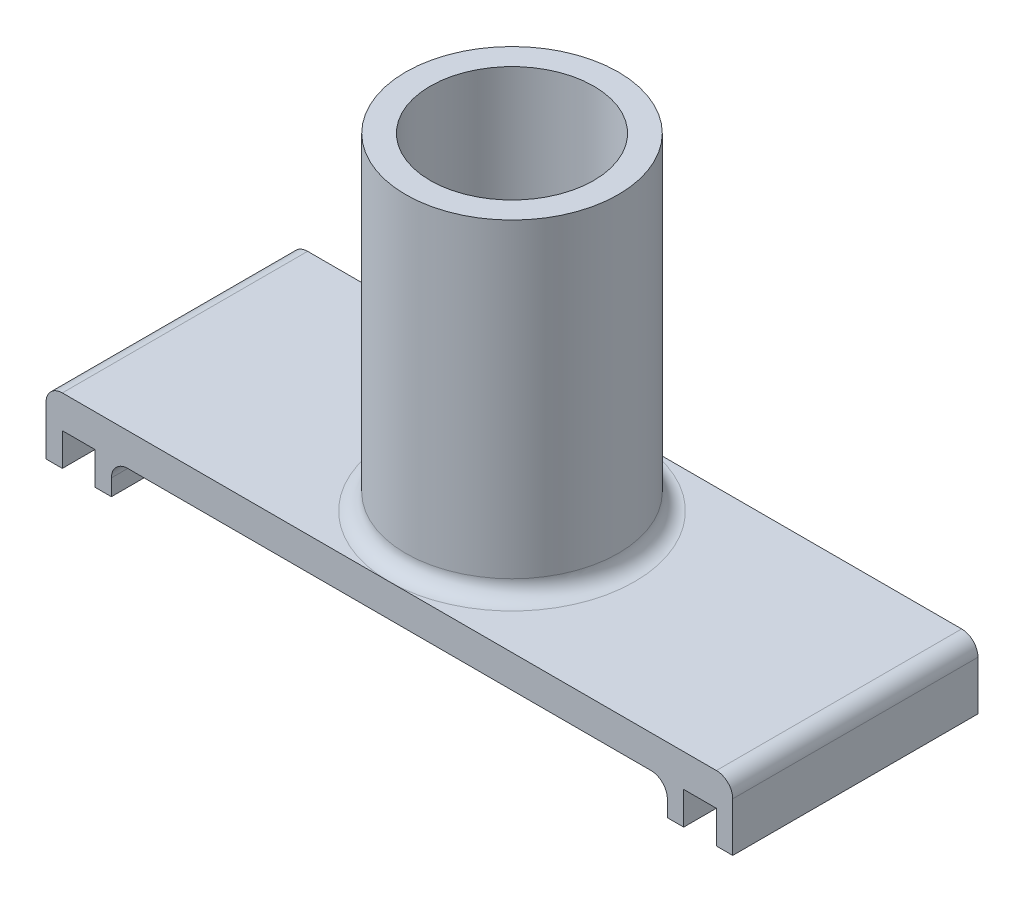
SolidWorks part; units mm, degrees
ref_plane "Front Plane" through (0, 0, 0) normal (0, 0, 1) x (1, 0, 0)
ref_plane "Top Plane" through (0, 0, 0) normal (0, 1, 0) x (1, 0, 0)
ref_plane "Right Plane" through (0, 0, 0) normal (1, 0, 0) x (0, 0, -1)
sketch "Sketch1" plane through (0, 0, 0) normal (0, 1, 0) x (1, 0, 0)
  line L1 (-210, -75) -> (210, -75)
  line L2 (-210, -75) -> (-210, 75)
  line L3 (-210, 75) -> (210, 75)
  line L4 (210, -75) -> (210, 75)
  line L5 (-210, -75) -> (210, 75) construction
  line L6 (-210, 75) -> (210, -75) construction
  point P0 (0, 0)
extrude "Boss-Extrude1" add sketch "Sketch1" along normal blind 20
sketch "Sketch2" plane through (0, 0, 0) normal (0, -1, 0) x (1, 0, 0)
  line L0 (-210, 75) -> (210, 75) construction
  line L5 (180, -75) -> (180, 75)
  line L6 (180, -75) -> (170, -75)
  line L7 (-180, 75) -> (-200, 75)
  line L8 (200, -75) -> (200, 75)
  line L9 (-200, 75) -> (-210, 75)
  line L10 (-200, 75) -> (-200, -75)
  line L11 (-200, -75) -> (-210, -75)
  line L12 (-210, 75) -> (-210, -75)
  line L13 (200, -75) -> (210, -75)
  line L14 (210, -75) -> (210, 75)
  line L15 (200, 75) -> (210, 75)
  line L24 (170, -75) -> (170, 75)
  line L25 (-180, 75) -> (-170, 75)
  line L26 (-180, 75) -> (-180, -75)
  line L27 (-180, -75) -> (-170, -75)
  line L28 (-170, 75) -> (-170, -75)
  line L29 (180, 75) -> (170, 75)
  point P0 (0, 0)
  point P23 (0, 0)
  point P28 (0, 0)
  line M10 (210, -75) -> (210, 75)
  line M11 (210, 75) -> (-210, 75)
  line M12 (-210, 75) -> (-210, -75)
  line M13 (-210, -75) -> (210, -75)
  dimension "D1" = 2
  dimension "D2" = 2
extrude "Boss-Extrude3" add sketch "Sketch2" along normal blind 20 contours L10 M11 M12 M13 | L28 L26 M11 M13 | L8 M13 M10 M11 | L5 L29 L24 L6 region at (205, 0, 0) region at (-175, 0, 0) region at (-205, 0, 0)
fillet "Fillet1" radius 10 1 edges at (-170, 0, 0)
fillet "Fillet2" radius 10 1 edges at (170, 0, 0)
fillet "Fillet3" radius 10 1 edges at (210, 20, 0)
fillet "Fillet4" radius 10 1 edges at (-210, 20, 0)
sketch "Sketch3" plane through (0, 20, 0) normal (0, 1, 0) x (1, 0, 0)
  circle A0 centre (0, 0) radius 50
  circle A1 centre (0, 0) radius 65
extrude "Boss-Extrude4" add sketch "Sketch3" along normal blind 200
fillet "Fillet5" radius 10 1 edges at (0, 20, -65)
sketch "Sketch4" plane through (0, 220, 0) normal (0, 1, 0) x (1, 0, 0)
  circle A0 centre (0, 0) radius 50
extrude "Cut-Extrude1" cut sketch "Sketch4" against normal blind 327
